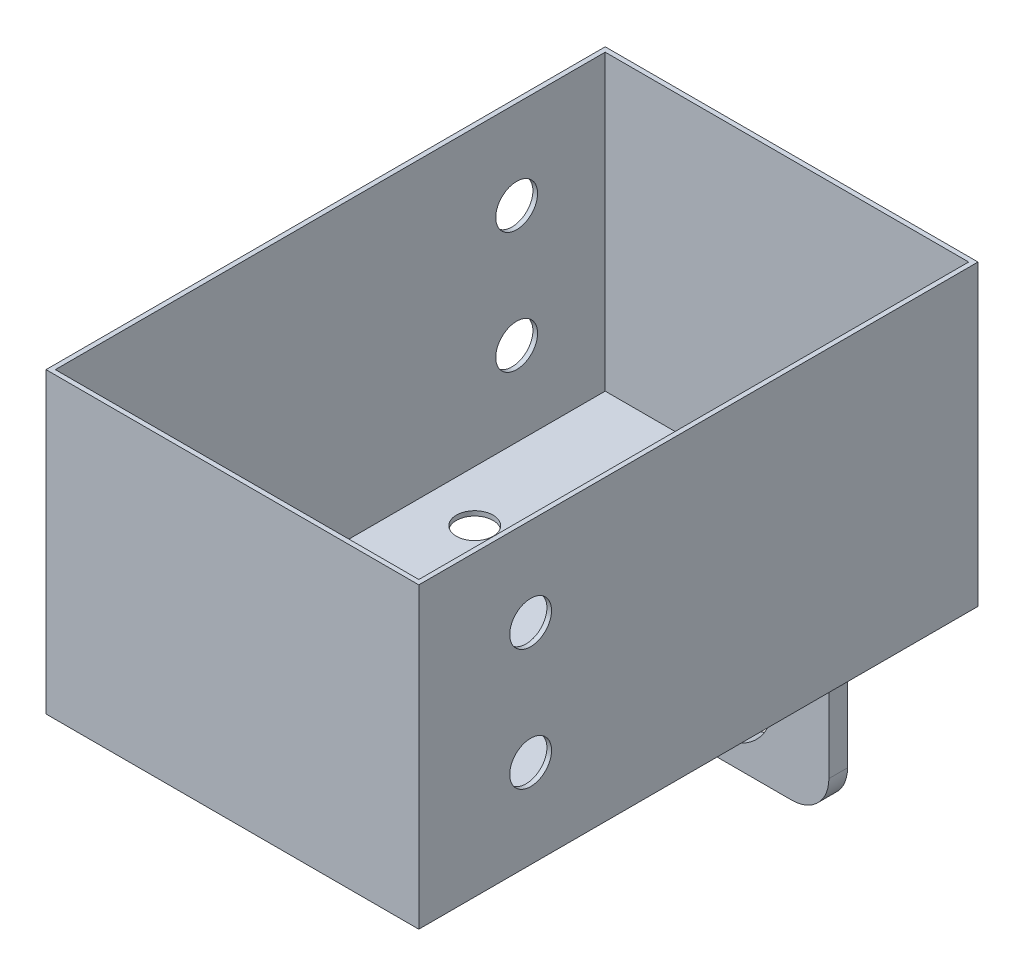
SolidWorks part; units mm, degrees
ref_plane "Front" through (0, 0, 0) normal (0, 0, 1) x (1, 0, 0)
ref_plane "Top" through (0, 0, 0) normal (0, 1, 0) x (1, 0, 0)
ref_plane "Right" through (0, 0, 0) normal (1, 0, 0) x (0, 0, -1)
ref_axis "Axis1" through (0, 0, 55) along (0, 0, -1)
sketch "Sketch1" plane through (0, 0, 0) normal (0, 1, 0) x (1, 0, 0)
  line L1 (-127, 190.5) -> (127, 190.5)
  line L2 (-127, 190.5) -> (-127, -190.5)
  line L3 (-127, -190.5) -> (127, -190.5)
  line L4 (127, 190.5) -> (127, -190.5)
  line L5 (-127, 190.5) -> (127, -190.5) construction
  line L6 (-127, -190.5) -> (127, 190.5) construction
  point P0 (0, 0)
  dimension "D1" = 254
  dimension "D2" = 381
extrude "Boss-Extrude1" add sketch "Sketch1" along normal blind 203.2
shell "Shell1" thickness 3.175 removed face at (0, 203.2, 0)
sketch "Sketch2" plane through (127, 0, 0) normal (1, 0, 0) x (0, 0, -1)
  line L0 (-190.5, 101.6) -> (190.5, 101.6) construction
  line L1 (-190.5, 203.2) -> (-190.5, 0) construction
  line L2 (190.5, 203.2) -> (190.5, 0) construction
  line L3 (-114.3, 203.2) -> (-114.3, 0) construction
  line L4 (-190.5, 203.2) -> (190.5, 203.2) construction
  line L5 (-190.5, 0) -> (190.5, 0) construction
  circle A0 centre (-114.3, 142.875) radius 14.25
  circle A1 centre (-114.3, 60.325) radius 14.25
  dimension "D1" = 28.5
  dimension "D2" = 82.55
  dimension "D3" = 76.2
extrude "Cut-Extrude1" cut sketch "Sketch2" against normal up to next
sketch "Sketch3" plane through (-127, 0, 0) normal (-1, 0, 0) x (0, 0, 1)
  line L0 (-190.5, 101.6) -> (190.5, 101.6) construction
  line L1 (-190.5, 203.2) -> (-190.5, 0) construction
  line L2 (190.5, 203.2) -> (190.5, 0) construction
  line L3 (-127, 203.2) -> (-127, 0) construction
  line L4 (-190.5, 203.2) -> (190.5, 203.2) construction
  line L5 (-190.5, 0) -> (190.5, 0) construction
  circle A0 centre (-127, 142.875) radius 14.25
  circle A1 centre (-127, 60.325) radius 14.25
  dimension "D2" = 28.5
  dimension "D1" = 63.5
  dimension "D3" = 82.55
extrude "Cut-Extrude2" cut sketch "Sketch3" against normal up to next
sketch "Sketch4" plane through (0, 0, 0) normal (0, -1, 0) x (1, 0, 0)
  line L0 (0, -190.5) -> (0, 190.5) construction
  line L1 (127, -190.5) -> (-127, -190.5) construction
  line L2 (-127, 190.5) -> (127, 190.5) construction
  line L4 (76.2, -152.4) -> (-76.2, -152.4)
  line L5 (76.2, -152.4) -> (76.2, -139.7)
  line L6 (76.2, -139.7) -> (-76.2, -139.7)
  line L7 (-76.2, -152.4) -> (-76.2, -139.7)
  line L8 (76.2, -152.4) -> (-76.2, -139.7) construction
  line L9 (76.2, -139.7) -> (-76.2, -152.4) construction
  point P6 (0, -146.05)
  dimension "D1" = 330.2
  dimension "D2" = 152.4
  dimension "D3" = 12.7
extrude "Boss-Extrude2" add sketch "Sketch4" along normal blind 127
sketch "Sketch5" plane through (0, 0, -152.4) normal (0, 0, -1) x (-1, 0, 0)
  line L0 (0, -127) -> (0, 0) construction
  line L1 (76.2, -127) -> (-76.2, -127) construction
  line L2 (76.2, 0) -> (-76.2, 0) construction
  circle A0 centre (0, -76.2) radius 38.1
  dimension "D1" = 76.2
  dimension "D2" = 76.2
extrude "Cut-Extrude3" cut sketch "Sketch5" against normal up to next
fillet "Fillet1" radius 25.4 2 edges at (-76.2, -127, -146.05) (76.2, -127, -146.05)
fillet "Fillet2" radius 25.4 1 edges at (0, 0, -139.7)
sketch "Sketch6" plane through (0, 0, 0) normal (0, -1, 0) x (1, 0, 0)
  line L0 (0, 190.5) -> (0, -190.5) construction
  line L1 (-127, 190.5) -> (127, 190.5) construction
  line L2 (127, -190.5) -> (-127, -190.5) construction
  line L3 (-127, -63.5) -> (127, -63.5) construction
  line L4 (-127, -190.5) -> (-127, 190.5) construction
  line L5 (127, 190.5) -> (127, -190.5) construction
  line L6 (0, 165.1) -> (127, 165.1) construction
  line L7 (101.6, -63.5) -> (101.6, -160.02) construction
  circle A0 centre (63.5, 165.1) radius 6.35
  circle A2 centre (-88.9, -63.5) radius 12.5
  circle A3 centre (101.6, -160.02) radius 12.5
  dimension "D1" = 12.7
  dimension "D5" = 25
  dimension "D7" = 25
  dimension "D2" = 25.4
  dimension "D3" = 25.4
  dimension "D4" = 127
  dimension "D6" = 96.52
  dimension "D8" = 88.9
extrude "Cut-Extrude4" cut sketch "Sketch6" against normal up to next
